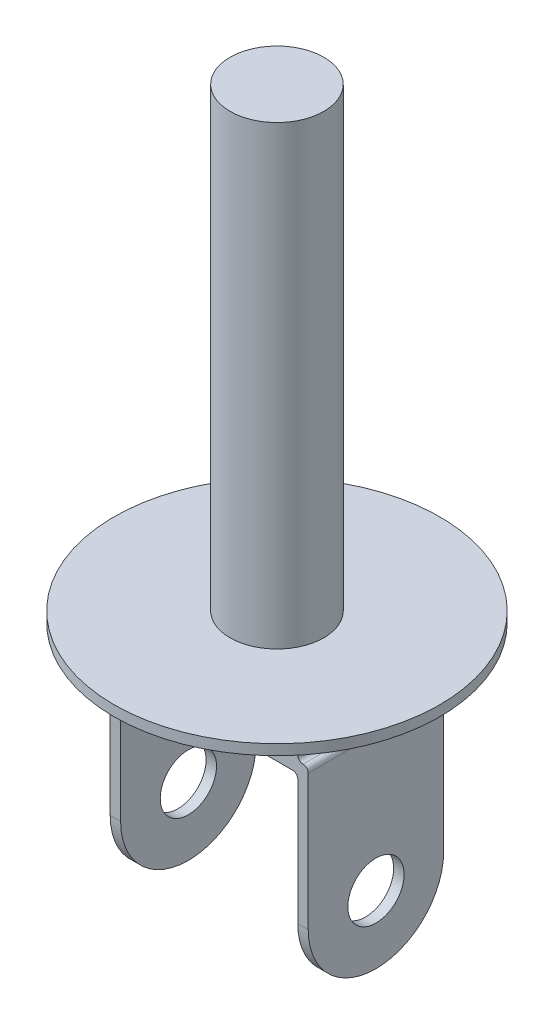
SolidWorks part; units mm, degrees
material "AISI 1020 Steel, Cold Rolled"
ref_plane "Front Plane" through (0, 0, 0) normal (0, 0, 1) x (1, 0, 0)
ref_plane "Top Plane" through (0, 0, 0) normal (0, 1, 0) x (1, 0, 0)
ref_plane "Right Plane" through (0, 0, 0) normal (1, 0, 0) x (0, 0, -1)
sketch "Sketch1" plane through (0, 0, 0) normal (0, 1, 0) x (1, 0, 0)
  circle A0 centre (0, 0) radius 31.25
  dimension "D1" = 62.5
extrude "Boss-Extrude1" add sketch "Sketch1" along normal blind 2
sketch "Sketch2" plane through (0, 0, 0) normal (0, -1, 0) x (1, 0, 0)
  line L1 (-19, -13) -> (19, -13)
  line L2 (-19, -13) -> (-19, 13)
  line L3 (-19, 13) -> (19, 13)
  line L4 (19, -13) -> (19, 13)
  line L5 (-19, -13) -> (19, 13) construction
  line L6 (-19, 13) -> (19, -13) construction
  point P0 (0, 0)
  dimension "D1" = 38
  dimension "D2" = 26
extrude "Boss-Extrude2" add sketch "Sketch2" along normal blind 48
sketch "Sketch3" plane through (0, 0, 13) normal (0, 0, 1) x (1, 0, 0)
  line L0 (19, -48) -> (-19, -48) construction
  line L1 (-17, -10) -> (17, -10)
  line L2 (-17, -10) -> (-17, -48)
  line L3 (-17, -48) -> (17, -48)
  line L4 (17, -10) -> (17, -48)
  line L5 (-17, -10) -> (17, -48) construction
  line L6 (-17, -48) -> (17, -10) construction
  line L7 (-19, -48) -> (-19, 0) construction
  line L8 (19, -48) -> (19, 0) construction
  line L9 (19, 0) -> (-19, 0) construction
  point P0 (0, -29)
  dimension "D1" = 2
  dimension "D2" = 2
  dimension "D3" = 10
extrude "Cut-Extrude1" cut sketch "Sketch3" against normal blind 48
sketch "Sketch4" plane through (19, 0, 0) normal (1, 0, 0) x (0, 0, -1)
  line L0 (-13, -48) -> (-13, 0) construction
  line L1 (13, -48) -> (-13, -48) construction
  circle A0 centre (0, -35) radius 13
  line M3 (-13, 0) -> (-13, -48)
  line M4 (-13, -48) -> (13, -48)
  line M5 (13, -48) -> (13, 0)
extrude "Cut-Extrude2" cut sketch "Sketch4" against normal blind 48 contours A0 M3 M4 | A0 M4 M5
hole_wizard "M12x1.25 Tapped Hole1" positions "Sketch5" profile "Sketch6" tap size "M12x1.25" standard "ANSI Metric" end condition through all
sketch "Sketch5" plane through (19, 0, 0) normal (1, 0, 0) x (0, 0, -1)
  point P0 (0, -35)
sketch "Sketch6" plane through (19, -35, 0) normal (0, 1, 0) x (0, 0, -1)
  line L0 (0, 0) -> (0, 50.25)
  line L1 (0, 50.25) -> (5.4, 50.25)
  line L2 (5.4, 50.25) -> (5.4, 0)
  line L5 (5.4, 0) -> (0, 0)
  line L11 (0, -6.35) -> (0, 107.95) construction
  dimension "Thru Tap Drill Dia." = 10.8
  dimension "Thru Tap Drill Depth" = 50.25
cosmetic thread "Hole Thread1" parameters "D2"=12
sketch "Sketch7" plane through (0, 0, -13) normal (0, 0, -1) x (-1, 0, 0)
  line L0 (-19, -35) -> (-19, 0) construction
  line L1 (-19, -2) -> (-17, -2)
  line L2 (-19, -2) -> (-19, -8)
  line L3 (-19, -8) -> (-17, -8)
  line L4 (-17, -2) -> (-17, -8)
  line L5 (19, 0) -> (-19, 0) construction
  line L6 (-17, -10) -> (17, -10) construction
  line L7 (19, -35) -> (19, 0) construction
  line L8 (19, -2) -> (17, -2)
  line L9 (19, -2) -> (19, -8)
  line L10 (19, -8) -> (17, -8)
  line L11 (17, -2) -> (17, -8)
  dimension "D1" = 2
  dimension "D2" = 2
  dimension "D3" = 2
  dimension "D4" = 2
  dimension "D5" = 6
  dimension "D6" = 2
extrude "Cut-Extrude3" cut sketch "Sketch7" against normal blind 48
fillet "Fillet2" radius 1 12 edges at (17, -10, 0) (-17, -10, 0) (19, -8, 0) (17, -8, 0) (17, -2, 0) (19, -2, 0) (19, 0, 0) (-19, 0, 0) (-19, -2, 0) (-17, -2, 0) (-17, -8, 0) (-19, -8, 0)
sketch "Sketch8" plane through (0, 2, 0) normal (0, 1, 0) x (1, 0, 0)
  circle A0 centre (0, 0) radius 9
  dimension "D1" = 18
extrude "Boss-Extrude3" add sketch "Sketch8" along normal blind 87.5
